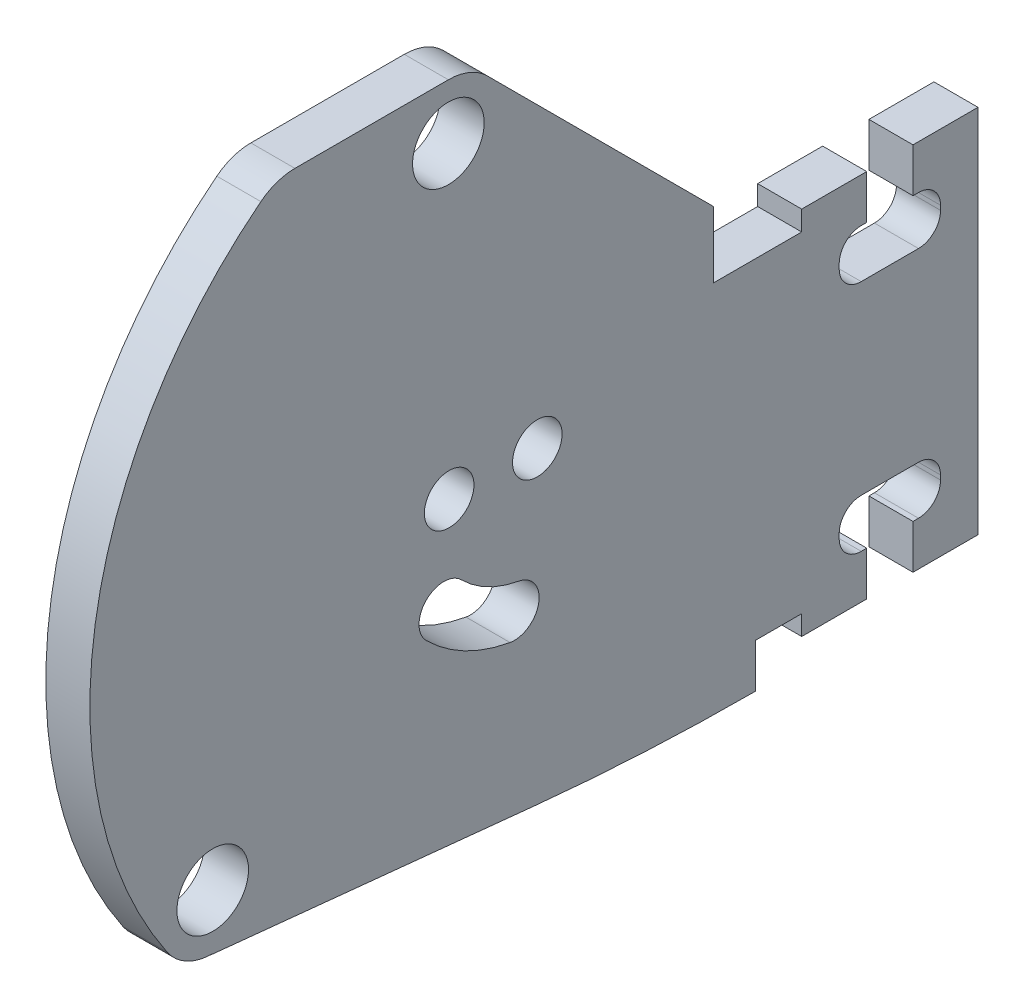
SolidWorks part; units mm, degrees
ref_plane "Front Plane" through (0, 0, 0) normal (0, 0, 1) x (1, 0, 0)
ref_plane "Top Plane" through (0, 0, 0) normal (0, 1, 0) x (1, 0, 0)
ref_plane "Right Plane" through (0, 0, 0) normal (1, 0, 0) x (0, 0, -1)
sketch "Sketch1" plane through (0, 0, 0) normal (1, 0, 0) x (0, 0, -1)
  line L0 (-16, 7.5) -> (20, 7.5) construction
  line L1 (-16, 15) -> (20, 15)
  line L2 (-16, 15) -> (-16, 0)
  line L3 (-16, 0) -> (20, 0)
  line L4 (20, 15) -> (20, 0)
  line L5 (0, 15) -> (0, 0) construction
  line L10 (0, 12.5) -> (-4.2426, 8.2574) construction
  line L11 (8, 15) -> (8, 18)
  line L12 (8, 18) -> (-5.9213, 31.9213)
  line L13 (20, 15) -> (12, 15)
  line L14 (20, 15) -> (20, 15.9)
  line L15 (20, 15.9) -> (12, 15.9)
  line L16 (12, 15) -> (12, 15.9)
  line L18 (16, 15.9) -> (16, -0.9) construction
  line L19 (20, 0) -> (12, 0)
  line L20 (20, 0) -> (20, -0.9)
  line L21 (20, -0.9) -> (12, -0.9)
  line L22 (12, 0) -> (12, -0.9)
  line L23 (14.95, 1.1) -> (17.05, 1.1)
  line L24 (14.95, 13.9) -> (17.05, 13.9)
  line L25 (14.95, 13.9) -> (14.95, 15.9)
  line L26 (14.95, 15.9) -> (17.05, 15.9)
  line L27 (17.05, 13.9) -> (17.05, 15.9)
  line L28 (14.95, 13.9) -> (17.05, 15.9) construction
  line L29 (14.95, 15.9) -> (17.05, 13.9) construction
  line L30 (13.7, 11.7) -> (18.3, 11.7)
  line L31 (13.7, 11.7) -> (13.7, 13.9)
  line L32 (13.7, 13.9) -> (18.3, 13.9)
  line L33 (18.3, 11.7) -> (18.3, 13.9)
  line L34 (13.7, 11.7) -> (18.3, 13.9) construction
  line L35 (13.7, 13.9) -> (18.3, 11.7) construction
  line L36 (14.95, 1.1) -> (14.95, -0.9)
  line L37 (14.95, -0.9) -> (17.05, -0.9)
  line L38 (17.05, 1.1) -> (17.05, -0.9)
  line L39 (13.7, 3.3) -> (13.7, 1.1)
  line L40 (13.7, 1.1) -> (18.3, 1.1)
  line L41 (18.3, 3.3) -> (18.3, 1.1)
  line L42 (13.7, 3.3) -> (18.3, 3.3)
  line L43 (-3, 29) -> (-11.8322, 29)
  line L44 (0, 12.5) -> (-1.2372, 5.4832) construction
  line L45 (4.9, -2) -> (-14.982, 0.0127)
  line L46 (9.9, 0) -> (4.9, 0)
  line L47 (9.9, 0) -> (9.9, -2)
  line L48 (9.9, -2) -> (4.9, -2)
  line L49 (4.9, 0) -> (4.9, -2)
  circle A2 centre (0, 12.5) radius 1.125
  circle A12 centre (-4.2426, 8.2574) radius 1.125
  circle A14 centre (0, 12.5) radius 20.3039
  circle A15 centre (0, 12.5) radius 4.875
  circle A16 centre (0, 12.5) radius 7.125
  circle A17 centre (-14.7303, 2.5) radius 2.5
  circle A18 centre (-14.7303, 2.5) radius 1.625
  circle A19 centre (-4.0355, 26.5) radius 2.5
  circle A20 centre (-4.0355, 26.5) radius 1.625
  circle A21 centre (-10.9991, 26.5) radius 2.5
  circle A22 centre (-1.0419, 6.5912) radius 1.125
  circle A23 centre (-4, 12.5) radius 1.125
  point P15 (16, 14.9)
  point P34 (16, 12.8)
  point P65 (0, 0)
  dimension "D1" = 2.25
  dimension "D2" = 5
  dimension "D7" = 6
  dimension "D11" = 2.1
  dimension "D16" = 5
  dimension "D17" = 3.25
  dimension "D3" = 15
  dimension "D4" = 20
  dimension "D5" = 16
  dimension "D6" = 45
  dimension "D8" = 8
  dimension "D9" = 0.9
  dimension "D10" = 8
  dimension "D12" = 2
  dimension "D13" = 2.2
  dimension "D14" = 4.6
  dimension "D15" = 3
  dimension "D18" = 14
  dimension "D19" = 10
  dimension "D20" = 0.9
  dimension "D21" = 2
  dimension "D22" = 5
  dimension "D23" = 6.1
  dimension "D24" = 4
extrude "Base shape" add sketch "Sketch1" along normal blind 2 contours A16 L1 L11 L12 A14 L2 | A16 L1 L2 L3 L36 L40 L39 L42 L41 A14 L4 L27 L32 L33 L30 L31 L25 | L1 A16 A15 | L1 A16 A12 A15 | L1 A15 A2 | L1 A15 | A16 L1 A15 | A14 L38 L3 L4 L41 L40 | L3 L38 L21 L20 | L36 L3 L22 L21 | L1 L25 L15 L16 | A18 L2 A17 | A18 L2 A17 | A19 A20 | A21 | A14 L14 L15 | L3 L49 L48 L47 | L49 L3 L45 region at (0, 14.61, -10) region at (0, 18.7739, 9.6278) region at (0, 15.45, -13.475) region at (0, 9.6923, -4.2211) region at (0, 15.1412, -5.4286) region at (0, 13.7643, -4.582) region at (0, 15.9731, 0) region at (0, 11.8743, 5.7401) region at (0, 27.4296, 1.7912) region at (0, 15.45, -18.525) region at (0, 4.6164, 13.5212) region at (0, 2.5, 16.5586) region at (0, 26.5, 10.9991) region at (0, 2.8412, -19.0769) region at (0, -0.45, -18.525) region at (0, -0.6667, 1.6855) region at (0, -1, -7.4) region at (0, -0.45, -13.475)
fillet "Bottom fillet" radius 100 1 edges at (1, -2, -4.9)
fillet "Fillet1" radius 1 8 edges at (1, 13.9, -13.7) (1, 11.7, -13.7) (1, 11.7, -18.3) (1, 13.9, -18.3) (1, 1.1, -18.3) (1, 3.3, -18.3) (1, 1.1, -13.7) (1, 3.3, -13.7)
